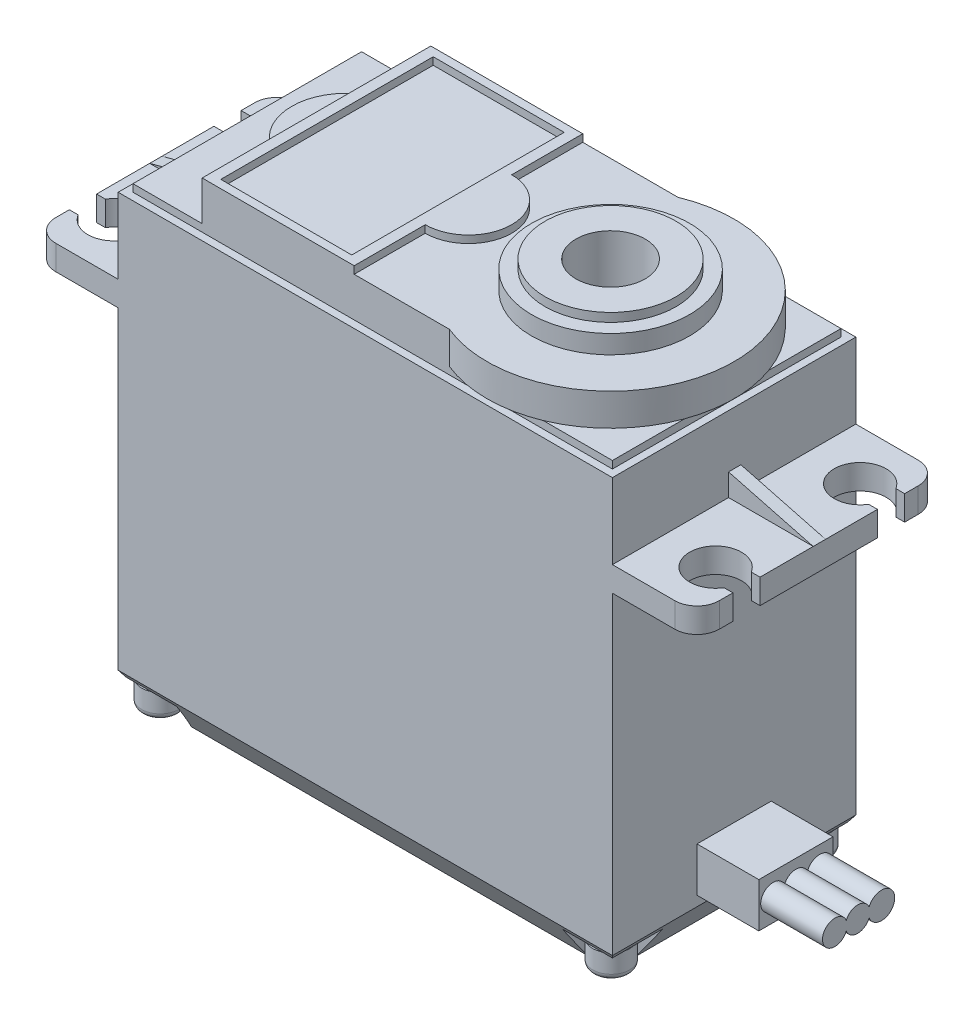
SolidWorks part; units mm, degrees
ref_plane "Front Plane" through (0, 0, 0) normal (0, 0, 1) x (1, 0, 0)
ref_plane "Top Plane" through (0, 0, 0) normal (0, 1, 0) x (1, 0, 0)
ref_plane "Right Plane" through (0, 0, 0) normal (1, 0, 0) x (0, 0, -1)
sketch "Sketch1" plane through (0, 0, 0) normal (0, 0, 1) x (1, 0, 0)
  line L1 (20, -18.25) -> (-20, -18.25)
  line L2 (20, -18.25) -> (20, 18.25)
  line L3 (20, 18.25) -> (-20, 18.25)
  line L4 (-20, -18.25) -> (-20, 18.25)
  line L5 (20, -18.25) -> (-20, 18.25) construction
  line L6 (20, 18.25) -> (-20, -18.25) construction
  point P0 (0, 0)
  dimension "D1" = 40
  dimension "D2" = 36.5
extrude "Boss-Extrude1" add sketch "Sketch1" along normal blind 19.7 contours L4 L3 L2 L1
chamfer "Chamfer1" distance 2 distance2 3 4 edges at (0, -18.25, 0) (-20, -18.25, 9.85) (0, -18.25, 19.7) (20, -18.25, 9.85) first distance on face at (0, -18.25, 9.85)
sketch "Sketch2" plane through (0, -18.25, 0) normal (0, -1, 0) x (1, 0, 0)
  line L0 (20, 19.7) -> (20, 0) construction
  line L1 (-20, 19.7) -> (20, 19.7) construction
  line L2 (20, 0) -> (-20, 0) construction
  line L3 (-20, 0) -> (-20, 19.7) construction
  line L6 (20, 15.3) -> (20, 19.7)
  line L7 (20, 19.7) -> (15.6, 19.7)
  line L10 (20, 4.4) -> (20, 0)
  line L11 (20, 0) -> (15.6, 0)
  line L13 (-15.6, 0) -> (-20, 0)
  line L16 (-20, 0) -> (-20, 4.4)
  line L18 (-20, 15.3) -> (-20, 19.7)
  line L19 (-20, 19.7) -> (-15.6, 19.7)
  arc A0 (20, 15.3) -> (15.6, 19.7) centre (20, 19.7) cw
  arc A1 (20, 4.4) -> (15.6, 0) centre (20, 0) ccw
  arc A2 (-20, 4.4) -> (-15.6, 0) centre (-20, 0) cw
  arc A3 (-15.6, 19.7) -> (-20, 15.3) centre (-20, 19.7) cw
  dimension "D1" = 4.4
extrude "Cut-Extrude1" cut sketch "Sketch2" against normal blind 2.5
sketch "Sketch4" plane through (0, -15.75, 0) normal (0, -1, 0) x (1, 0, 0)
  circle A0 centre (-18.295, 18.0012) radius 1.5
  circle A1 centre (18.205, 18.0012) radius 1.5
  circle A2 centre (18.205, 1.7512) radius 1.5
  circle A3 centre (-18.295, 1.7512) radius 1.5
  dimension "D1" = 3
  dimension "D2" = 2
  dimension "D3" = 2
extrude "Boss-Extrude2" add sketch "Sketch4" along normal blind 2 contours A1 | A2 | A3 | A0 region at (18.205, -15.75, 18.0012) region at (18.205, -15.75, 1.7512) region at (-18.295, -15.75, 1.7512)
fillet "Fillet1" radius 0.5 1 edges at (-16.795, -17.75, 18.0012)
fillet "Fillet3" radius 0.5 1 edges at (-16.795, -17.75, 1.7512)
fillet "Fillet4" radius 0.5 1 edges at (19.705, -17.75, 1.7512)
fillet "Fillet5" radius 0.5 1 edges at (19.705, -17.75, 18.0012)
ref_plane "Plane1" through (0, 10.15, 0) normal (0, -1, 0) x (-1, 0, 0)
sketch "Sketch5" plane through (0, 10.15, 0) normal (0, -1, 0) x (-1, 0, 0)
  line L0 (20, -19.7) -> (-20, 0)
  line L1 (20, -19.7) -> (-20, -19.7)
  line L2 (20, -19.7) -> (20, 0)
  line L3 (20, 0) -> (-20, 0)
  line L4 (-20, -19.7) -> (-20, 0)
  line L5 (-20, -19.7) -> (20, 0)
  line L7 (26.85, 0) -> (-26.85, 0)
  line L8 (26.85, 0) -> (26.85, -19.7)
  line L9 (26.85, -19.7) -> (-26.85, -19.7)
  line L10 (-26.85, 0) -> (-26.85, -19.7)
  line L11 (26.85, 0) -> (-26.85, -19.7) construction
  line L12 (26.85, -19.7) -> (-26.85, 0) construction
  point P6 (0, -9.85)
  dimension "D1" = 53.7
extrude "Boss-Extrude3" add sketch "Sketch5" against normal blind 2 contours L10 L9 L8 L7
sketch "Sketch6" plane through (0, 10.15, 0) normal (0, -1, 0) x (1, 0, 0)
  line L0 (-20, 19.7) -> (-26.85, 19.7) construction
  line L1 (26.85, 14.6) -> (26.1389, 14.6)
  line L2 (26.85, 0) -> (26.85, 19.7) construction
  line L3 (26.85, 14.6) -> (26.85, 16.8)
  line L4 (26.85, 2.9) -> (26.1389, 2.9)
  line L5 (0, 19.7) -> (0, 0) construction
  line L6 (26.85, 16.8) -> (26.1389, 16.8)
  line L7 (-20, 19.7) -> (20, 19.7) construction
  line L8 (26.85, 9.85) -> (-26.85, 9.85) construction
  line L9 (-26.85, 0) -> (-26.85, 19.7) construction
  line L10 (26.85, 5.1) -> (26.85, 2.9)
  line L11 (26.85, 5.1) -> (26.1389, 5.1)
  line L12 (26.85, 0) -> (26.85, 19.7) construction
  line L14 (26.85, 0) -> (26.85, 19.7) construction
  line L15 (-26.85, 5.1) -> (-26.1389, 5.1)
  line L16 (-26.85, 5.1) -> (-26.85, 2.9)
  line L17 (-26.85, 16.8) -> (-26.1389, 16.8)
  line L18 (-26.85, 2.9) -> (-26.1389, 2.9)
  line L19 (-26.85, 14.6) -> (-26.85, 16.8)
  line L20 (-26.85, 14.6) -> (-26.1389, 14.6)
  arc A0 (26.1389, 16.8) -> (26.1389, 14.6) centre (24.35, 15.7) ccw
  arc A1 (26.1389, 2.9) -> (26.1389, 5.1) centre (24.35, 4) cw
  arc A2 (-26.1389, 2.9) -> (-26.1389, 5.1) centre (-24.35, 4) ccw
  arc A3 (-26.1389, 16.8) -> (-26.1389, 14.6) centre (-24.35, 15.7) cw
  point P15 (26.85, 15.7)
  point P28 (26.85, 4)
  point P39 (-26.85, 4)
  point P40 (-26.85, 15.7)
  dimension "D1" = 4.2
  dimension "D2" = 4
  dimension "D3" = 2.2
  dimension "D4" = 2.5
  dimension "D5" = 2.5
  dimension "D6" = 0.7111
extrude "Cut-Extrude2" cut sketch "Sketch6" against normal blind 2
fillet "Fillet9" radius 1.8 4 edges at (26.85, 11.15, 0) (-26.85, 11.15, 0) (-26.85, 11.15, 19.7) (26.85, 11.15, 19.7)
ref_plane "Plane2" through (0, 0, 10.3) normal (0, 0, 1) x (1, 0, 0)
sketch "Sketch7" plane through (0, 0, 10.3) normal (0, 0, 1) x (1, 0, 0)
  line L0 (-26.85, 12.15) -> (-20, 13.95)
  line L2 (-26.85, 12.15) -> (-20, 12.15)
  line L3 (-20, 12.15) -> (-20, 13.95)
  line L4 (0, -1000) -> (0, 49000) construction
  line L5 (20, 12.15) -> (20, 13.95)
  line L6 (26.85, 12.15) -> (20, 12.15)
  line L7 (26.85, 12.15) -> (20, 13.95)
  dimension "D1" = 1.8
extrude "Boss-Extrude4" add sketch "Sketch7" against normal blind 1
sketch "Sketch8" plane through (0, 18.25, 0) normal (0, 1, 0) x (1, 0, 0)
  line L0 (20, -19.7) -> (-20, 0) construction
  line L1 (20, 0) -> (-20, -19.7) construction
  line L2 (20, -19.7) -> (-20, -19.7) construction
  line L3 (-19.4, -0.6) -> (19.4, -0.6)
  line L4 (-19.4, -0.6) -> (-19.4, -19.1)
  line L5 (-19.4, -19.1) -> (19.4, -19.1)
  line L6 (19.4, -0.6) -> (19.4, -19.1)
  line L7 (-19.4, -0.6) -> (19.4, -19.1) construction
  line L8 (-19.4, -19.1) -> (19.4, -0.6) construction
  line L9 (20, -10.3) -> (20, -19.7) construction
  point P8 (0, -9.85)
  point P9 (0, -9.85)
  dimension "D1" = 0.6
  dimension "D2" = 0.6
extrude "Boss-Extrude5" add sketch "Sketch8" along normal blind 0.6 contours L6 L5 L4 L3
sketch "Sketch9" plane through (0, 18.85, 0) normal (0, 1, 0) x (1, 0, 0)
  line L0 (20, -19.7) -> (20, 0) construction
  line L1 (-13.7997, -6.1622) -> (-13.7997, -0.6)
  line L2 (6.2003, -19.1) -> (-13.7997, -19.1)
  line L3 (6.2003, -0.6) -> (-13.7997, -0.6)
  line L4 (-13.7997, -19.1) -> (-13.7997, -13.5378)
  line L5 (-19.4, -19.1) -> (19.4, -19.1) construction
  arc A0 (6.2003, -19.1) -> (6.2003, -0.6) centre (10, -9.85) ccw
  arc A1 (-13.7997, -6.1622) -> (-13.7997, -13.5378) centre (-11.3997, -9.85) ccw
  point P2 (20, -9.85)
  dimension "D1" = 10
  dimension "D2" = 20
  dimension "D4" = 8.8
  dimension "D3" = 20
  dimension "D5" = 2.4
extrude "Boss-Extrude6" add sketch "Sketch9" along normal blind 2.6
sketch "Sketch10" plane through (0, 21.45, 0) normal (0, 1, 0) x (1, 0, 0)
  line L0 (-13.7997, -19.1) -> (-13.7997, -0.6)
  line L1 (-13.7997, -19.1) -> (-1.4997, -19.1)
  line L2 (-13.7997, -0.6) -> (-1.4997, -0.6)
  line L3 (-1.4997, -19.1) -> (-1.4997, -13.35)
  line L4 (-13.7997, -9.85) -> (-1.4997, -9.85) construction
  line L5 (-12.9497, -1.2547) -> (-2.3497, -1.2547)
  line L6 (-12.9497, -1.2547) -> (-12.9497, -18.4453)
  line L7 (-12.9497, -18.4453) -> (-2.3497, -18.4453)
  line L8 (-2.3497, -1.2547) -> (-2.3497, -18.4453)
  line L9 (-12.9497, -1.2547) -> (-2.3497, -18.4453) construction
  line L10 (-12.9497, -18.4453) -> (-2.3497, -1.2547) construction
  line L11 (-7.6497, -19.1) -> (-7.6497, -0.6) construction
  line L12 (-1.4997, -6.35) -> (-1.4997, -0.6)
  arc A0 (-1.4997, -13.35) -> (-1.4997, -6.35) centre (-1.4997, -9.85) ccw
  point P0 (-7.6497, -9.85)
  dimension "D3" = 3.5
  dimension "D1" = 12.3
  dimension "D2" = 10.6
extrude "Boss-Extrude7" add sketch "Sketch10" along normal blind 0.6
sketch "Sketch11" plane through (0, 21.45, 0) normal (0, 1, 0) x (1, 0, 0)
  circle A0 centre (10, -9.85) radius 6.4
  dimension "D1" = 12.8
extrude "Boss-Extrude8" add sketch "Sketch11" along normal blind 1.5
sketch "Sketch12" plane through (0, 22.95, 0) normal (0, 1, 0) x (1, 0, 0)
  circle A0 centre (10, -9.85) radius 5.3
extrude "Boss-Extrude9" add sketch "Sketch12" along normal blind 0.7
sketch "Sketch13" plane through (0, 23.65, 0) normal (0, 1, 0) x (1, 0, 0)
  circle A0 centre (10, -9.85) radius 2.8
  dimension "D1" = 5.6
sketch "Sketch15" plane through (0, -17.75, 0) normal (0, -1, 0) x (1, 0, 0)
  line L0 (18.055, 1.6012) -> (18.055, 0.9012)
  line L1 (18.355, 2.6012) -> (18.055, 2.6012)
  line L2 (18.355, 2.6012) -> (18.355, 1.9012)
  line L3 (18.355, 0.9012) -> (18.055, 0.9012)
  line L4 (18.055, 2.6012) -> (18.055, 1.9012)
  line L5 (18.355, 2.6012) -> (18.055, 0.9012) construction
  line L6 (18.355, 0.9012) -> (18.055, 2.6012) construction
  line L7 (17.355, 1.6012) -> (18.055, 1.6012)
  line L8 (17.355, 1.6012) -> (17.355, 1.9012)
  line L9 (17.355, 1.9012) -> (18.055, 1.9012)
  line L10 (19.055, 1.6012) -> (19.055, 1.9012)
  line L11 (17.355, 1.6012) -> (19.055, 1.9012) construction
  line L12 (17.355, 1.9012) -> (19.055, 1.6012) construction
  line L13 (18.355, 1.6012) -> (19.055, 1.6012)
  line L14 (18.355, 1.9012) -> (19.055, 1.9012)
  line L15 (18.355, 1.6012) -> (18.355, 0.9012)
  point P0 (18.205, 1.7512)
  point P6 (18.205, 1.7512)
  dimension "D1" = 0.3
  dimension "D2" = 0.3
  dimension "D3" = 1.7
  dimension "D4" = 1.7
extrude "Cut-Extrude3" cut sketch "Sketch15" against normal blind 1.2
pattern_linear "LPattern1" count 2 spacing 36.5 along (-1, 0, 0) count 2 spacing 16.3 along (0, 0, 1) of "Cut-Extrude3"
sketch "Sketch16" plane through (20, 0, 0) normal (1, 0, 0) x (0, 0, -1)
  line L1 (-6.85, -10.85) -> (-12.85, -10.85)
  line L2 (-6.85, -10.85) -> (-6.85, -14.45)
  line L3 (-6.85, -14.45) -> (-12.85, -14.45)
  line L4 (-12.85, -10.85) -> (-12.85, -14.45)
  line L5 (-6.85, -10.85) -> (-12.85, -14.45) construction
  line L6 (-6.85, -14.45) -> (-12.85, -10.85) construction
  line L11 (-9.85, 18.25) -> (-9.85, -18.25) construction
  line L12 (-0.6, 18.25) -> (-19.1, 18.25) construction
  line L13 (-3.9192, -18.25) -> (-15.7808, -18.25) construction
  point P0 (-9.85, -12.65)
  dimension "D1" = 3.6
  dimension "D2" = 6
  dimension "D3" = 3.8
extrude "Boss-Extrude11" add sketch "Sketch16" along normal blind 5
sketch "Sketch17" plane through (25, 0, 0) normal (1, 0, 0) x (0, 0, -1)
  line L0 (-6.85, -14.45) -> (-6.85, -10.85) construction
  arc A0 (-10.775, -13.0016) -> (-8.925, -13.0016) centre (-9.85, -12.6216) ccw
  arc A1 (-8.925, -13.0016) -> (-8.925, -12.2417) centre (-7.9223, -12.6216) ccw
  arc A2 (-10.775, -12.2417) -> (-10.775, -13.0016) centre (-11.7, -12.6216) ccw
  arc A3 (-8.925, -12.2417) -> (-10.775, -12.2417) centre (-9.85, -12.6216) ccw
  dimension "D1" = 2
  dimension "D2" = 3
extrude "Boss-Extrude16" add sketch "Sketch17" along normal blind 5 contours A2 A0 A1 A3
extrude "Boss-Extrude42" add sketch "Sketch17<9>" along normal blind 5 contours A2 A0 A1 A3
sketch "Sketch17<9>" plane through (25, 0, 0) normal (1, 0, 0) x (0, 0, -1) same geometry as "Sketch17"
extrude "Cut-Extrude4" cut sketch "Sketch13" against normal up to surface (11.5 mm away) up to face at (-24.5791, 12.15, 4.003)
ref_plane "Plane3" through (0, 0, 9.85) normal (0, 0, 1) x (1, 0, 0)
